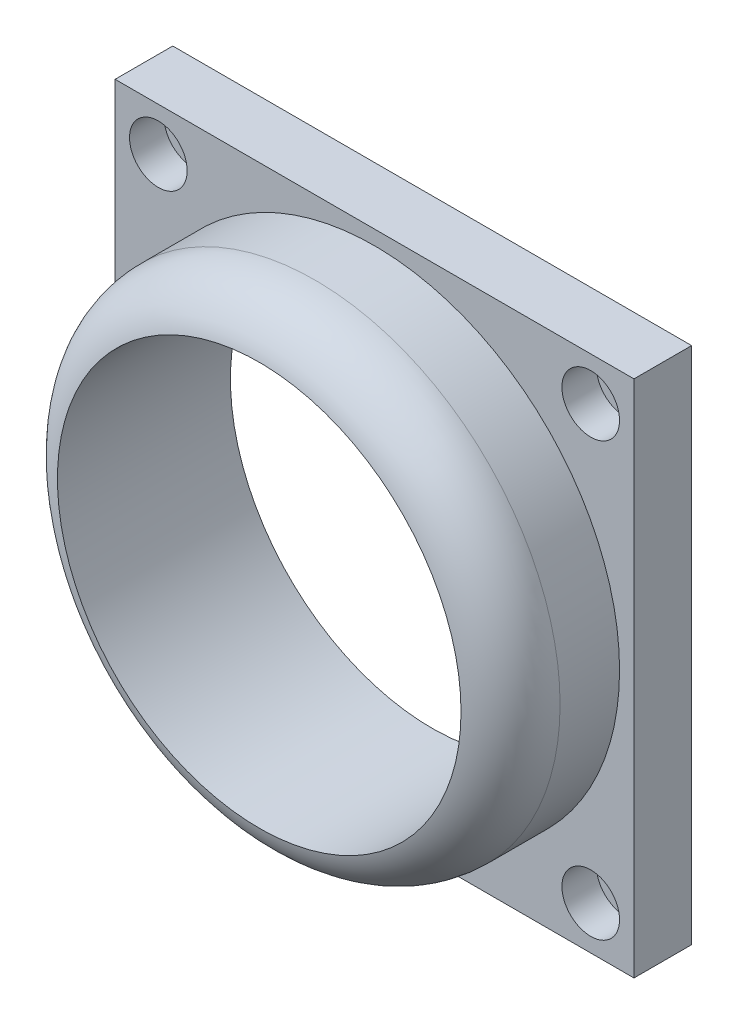
SolidWorks part; units mm, degrees
ref_plane "정면" through (0, 0, 0) normal (0, 0, 1) x (1, 0, 0)
ref_plane "윗면" through (0, 0, 0) normal (0, 1, 0) x (1, 0, 0)
ref_plane "우측면" through (0, 0, 0) normal (1, 0, 0) x (0, 0, -1)
sketch "스케치1" plane through (0, 0, 0) normal (0, 0, 1) x (1, 0, 0)
  line L1 (-92.7328, 73.1359) -> (-2.7328, 73.1359)
  line L2 (-92.7328, 73.1359) -> (-92.7328, -16.8641)
  line L3 (-92.7328, -16.8641) -> (-2.7328, -16.8641)
  line L4 (-2.7328, 73.1359) -> (-2.7328, -16.8641)
  line L5 (-92.7328, 73.1359) -> (-2.7328, -16.8641) construction
  line L6 (-92.7328, -16.8641) -> (-2.7328, 73.1359) construction
  point P0 (-47.7328, 28.1359)
  dimension "D1" = 90
  dimension "D2" = 90
extrude "보스-돌출3" add sketch "스케치1" along normal blind 10
sketch "스케치3" plane through (0, 0, 10) normal (0, 0, 1) x (1, 0, 0)
  circle A0 centre (-47.7328, 28.1359) radius 35
  dimension "D1" = 70
extrude "컷-돌출2" cut sketch "스케치3" against normal blind 10
sketch "스케치4" plane through (0, 0, 10) normal (0, 0, 1) x (1, 0, 0)
  circle A0 centre (-47.7328, 28.1359) radius 35
  circle A1 centre (-47.7328, 28.1359) radius 42.5
  dimension "D1" = 70
  dimension "D2" = 85
extrude "보스-돌출4" add sketch "스케치4" along normal blind 20
fillet "필렛1" radius 10 1 edges at (-5.2328, 28.1359, 30)
sketch "스케치5" plane through (0, 0, 10) normal (0, 0, 1) x (1, 0, 0)
  line L0 (-100.05, 28.1359) -> (5.4806, 28.1359) construction
  line L1 (-47.7328, 79.5366) -> (-47.7328, -26.8151) construction
  line L5 (-92.7328, 73.1359) -> (-92.7328, -16.8641) construction
  line L7 (-2.7328, 73.1359) -> (-92.7328, 73.1359) construction
  circle A4 centre (-85.2328, 65.6359) radius 3
  circle A5 centre (-10.2328, 65.6359) radius 3
  circle A6 centre (-10.2328, -9.3641) radius 3
  circle A7 centre (-85.2328, -9.3641) radius 3
  dimension "D1" = 6
  dimension "D2" = 75
  dimension "D3" = 75
  dimension "D4" = 7.5
  dimension "D5" = 7.5
extrude "컷-돌출3" cut sketch "스케치5" against normal blind 10
sketch "스케치6" plane through (0, 0, 10) normal (0, 0, 1) x (1, 0, 0)
  line L0 (-47.7328, 73.1359) -> (-47.7328, -22.3405) construction
  line L1 (-2.7328, 73.1359) -> (-92.7328, 73.1359) construction
  line L2 (-47.7328, 28.1359) -> (12.5015, 28.1359) construction
  circle A0 centre (-85.2328, 65.6359) radius 5
  circle A1 centre (-10.2328, 65.6359) radius 5
  circle A2 centre (-10.2328, -9.3641) radius 5
  circle A3 centre (-85.2328, -9.3641) radius 5
  dimension "D1" = 10
extrude "컷-돌출4" cut sketch "스케치6" against normal blind 6
